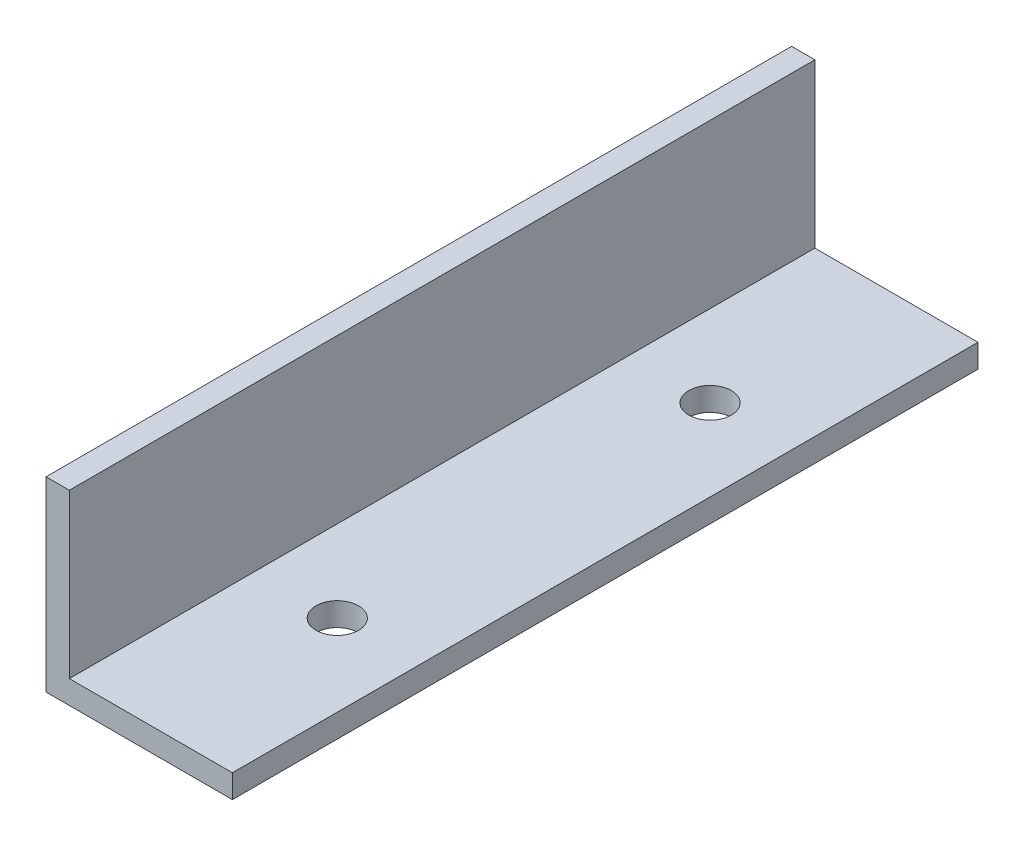
SolidWorks part; units mm, degrees
material "6061 Alloy"
ref_plane "Front Plane" through (0, 0, 0) normal (0, 0, 1) x (1, 0, 0)
ref_plane "Top Plane" through (0, 0, 0) normal (0, 1, 0) x (1, 0, 0)
ref_plane "Right Plane" through (0, 0, 0) normal (1, 0, 0) x (0, 0, -1)
sketch "Sketch1" plane through (0, 0, 0) normal (0, 0, 1) x (1, 0, 0)
  line L0 (0, 0) -> (25.4, 0)
  line L1 (0, 0) -> (0, 25.4)
  line L2 (3.175, 3.175) -> (25.4, 3.175)
  line L3 (3.175, 3.175) -> (3.175, 25.4)
  line L4 (0, 25.4) -> (3.175, 25.4)
  line L5 (25.4, 0) -> (25.4, 3.175)
  dimension "D1" = 25.4
  dimension "D2" = 25.4
  dimension "D3" = 3.175
extrude "Boss-Extrude1" add sketch "Sketch1" along normal blind 101.6
sketch "Sketch2" plane through (0, 0, 0) normal (0, 1, 0) x (1, 0, 0)
  line L0 (14.2875, -101.6) -> (14.2875, 0) construction
  line L1 (25.4, -101.6) -> (3.175, -101.6) construction
  line L2 (25.4, 0) -> (3.175, 0) construction
  circle A0 centre (14.2875, -25.4) radius 2.9
  circle A1 centre (14.2875, -76.2) radius 2.9
  dimension "D1" = 5.8
  dimension "D3" = 5.8
  dimension "D2" = 25.4
  dimension "D4" = 25.4
extrude "Cut-Extrude1" cut sketch "Sketch2" along normal blind 76.2
